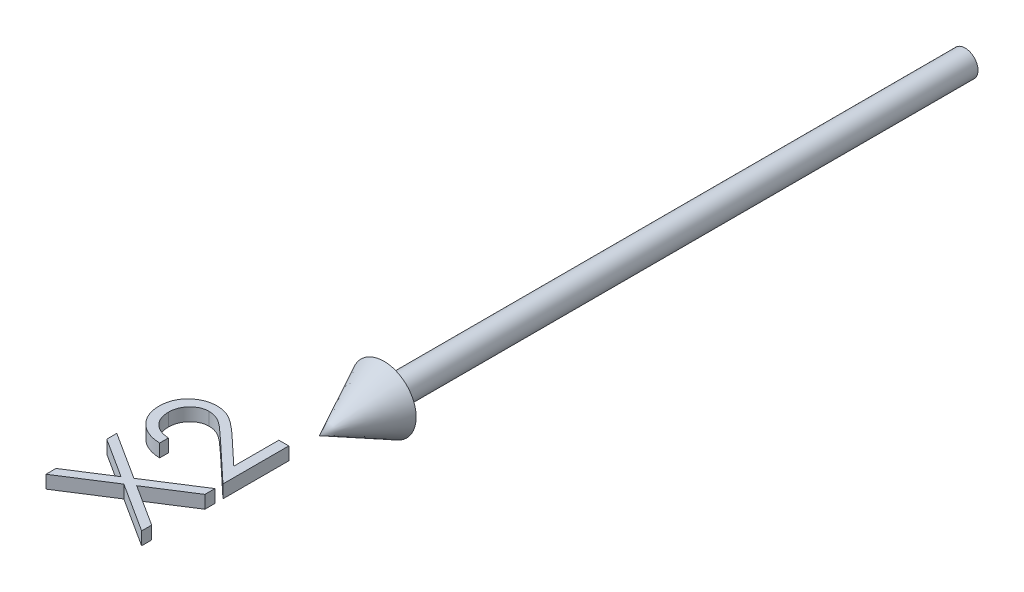
SolidWorks part; units mm, degrees
ref_plane "Front Plane" through (0, 0, 0) normal (0, 0, 1) x (1, 0, 0)
ref_plane "Top Plane" through (0, 0, 0) normal (0, 1, 0) x (1, 0, 0)
ref_plane "Right Plane" through (0, 0, 0) normal (1, 0, 0) x (0, 0, -1)
sketch "Sketch2" plane through (0, 0, 0) normal (0, 1, 0) x (1, 0, 0)
  line L0 (0, 41.95) -> (0, -114.4521) construction
  line L1 (-36.8894, 0) -> (41.4965, 0) construction
  line L2 (0, -100) -> (5, -90)
  line L3 (5, -90) -> (2, -90)
  line L4 (2, -90) -> (2, 0)
  line L5 (2, 0) -> (0, 0)
  line L6 (0, 0) -> (0, -100)
  dimension "D1" = 100
  dimension "D2" = 2
  dimension "D3" = 10
  dimension "D4" = 5
revolve "Revolve1" add sketch "Sketch2" angle 360 about L0
sketch "Sketch3" plane through (0, 0, 0) normal (0, 1, 0) x (1, 0, 0)
  line L0 (0, -103.9528) -> (0, -147.2622) construction
  line L1 (-18.6107, -118.3811) -> (18.3141, -118.3811) construction
  text T0 "X2" font "Century Gothic" height 15
extrude "Boss-Extrude1" add sketch "Sketch3" against normal blind 1 and the other way blind 1 separate body
equation "\"frame_arrow_length\"=100"
equation "\"D1@Sketch2\"=\"frame_arrow_length\""
equation "\"frame_arrow_odA\"=4"
equation "\"D2@Sketch2\"=\"frame_arrow_odA\"/2"
equation "\"frame_arrow_head_od\"=5"
equation "\"D4@Sketch2\"=\"frame_arrow_head_od\""
equation "\"frame_arrow_head_length\"=10"
equation "\"D3@Sketch2\"=\"frame_arrow_head_length\""
equation "\"tvarobot_theta1\"=30"
equation "\"link0_ringA_odA\"= 40"
equation "\"link0_ringA_odB\"= 25"
equation "\"link0_ringA_id\"= 20"
equation "\"link0_ringA_thickness\"= (\"link0_ringA_odB\" - \"link0_ringA_id\")/2"
equation "\"link0_ringA_height\"= 3"
equation "\"link0_ringA_heightA\"= 1.5"
equation "\"link0_ringA_heightB\"=\"link0_ringA_height\"-\"link0_ringA_heightA\""
equation "\"link0_ringB_odA\"= 40"
equation "\"link0_ringB_odB\"= 29"
equation "\"link0_ringB_id\"= \"link0_shaftA_bearing_id\"+1"
equation "\"link0_ringB_thickness\"= (\"link0_ringB_odB\" - \"link0_ringB_id\")/2"
equation "\"link0_ringB_height\"= 3"
equation "\"link0_ringB_heightA\"= 1.5"
equation "\"link0_ringB_heightB\"=\"link0_ringB_height\"-\"link0_ringB_heightA\""
equation "\"link0_shaftA_bearing_od\"=27"
equation "\"link0_shaftA_bearing_id\"=20"
equation "\"link0_shaftA_thrust_bearing_od\"=35"
equation "\"link0_shaftA_thrust_bearing_id\"=20.04"
equation "\"link0_shaftA_retaining_ring_id\"=18.5"
equation "\"link0_shaftA_retaining_ring_groove_width\"=1.5"
equation "\"link0_shaftA_spline_length\"=8.0"
equation "\"link0_shaftA_spline_depth\"=1.0"
equation "\"link0_shaftA_spline_width\"=4.0"
equation "\"link0_shaftA_odA\"=\"link0_shaftA_bearing_id\""
equation "\"link0_shaftA_odB\"=35"
equation "\"link0_shaftA_odC\"=\"link0_shaftA_bearing_id\""
equation "\"link0_shaftA_odD\"=\"link0_shaftA_odC\"-2*\"link0_shaftA_spline_depth\""
equation "\"link0_shaftA_odE\"=\"link0_shaftA_bearing_id\""
equation "\"link0_shaftA_odF\"=\"link0_shaftA_odE\"-2*\"link0_shaftA_spline_depth\""
equation "\"link0_shaftA_idA\"=10"
equation "\"link0_shaftA_idB\"=6"
equation "\"link0_shaftA_length\"=39.5"
equation "\"link0_shaftA_lengthA\"=8.0"
equation "\"link0_shaftA_lengthB\"=12.0"
equation "\"link0_shaftA_lengthC\"=35.0"
equation "\"link0_shaftA_lengthD\"=39.0"
equation "\"link0_shaftA_lengthE\"=\"link0_shaftA_length\"-\"link0_shaftA_lengthD\""
equation "\"link0_shaftA_offsetX\"=11"
equation "\"link0_shaftA_offsetY\"=0"
equation "\"link0_shaftA_bolt_pattern_dia\"=14"
equation "\"link0_motor_center_dist\"=26"
equation "\"link0_46t_pulley_spline_length\"=8"
equation "\"link0_46t_pulley_spline_depth\"=\"link0_shaftA_spline_depth\"*1.025"
equation "\"link0_46t_pulley_spline_width\"=\"link0_shaftA_spline_width\"*1.05"
equation "\"link0_46t_pulley_idA\"=\"link0_shaftA_bearing_id\"*1.025"
equation "\"link0_46t_pulley_idB\"=\"link0_46t_pulley_idA\"-2*\"link0_46t_pulley_spline_depth\""
equation "\"link0_shaftB_spline_length\"=10"
equation "\"link0_shaftB_spline_depth\"=1.0"
equation "\"link0_shaftB_spline_width\"=1.25"
equation "\"link0_shaftB_length\"=7"
equation "\"link0_shaftB_lengthA\"=1.5"
equation "\"link0_shaftB_lengthB\"=2.75"
equation "\"link0_shaftB_odA\"=32"
equation "\"link0_shaftB_odB\"=22"
equation "\"link0_shaftB_odC\"=20"
equation "\"link0_shaftB_idA\"=10"
equation "\"link0_shaftB_bolt_diameter\"=19"
equation "\"link0_shaftB_bearing_od\"=27"
equation "\"link0_shaftB_bearing_id\"=20"
equation "\"link0_motor_length\"=46.5"
equation "\"link0_motor_width\"=28.5"
equation "\"link0_motor_height\"=34"
equation "\"link0_motor_offset\"=8"
equation "\"link0_shellA_thickness\"=2.5"
equation "\"link0_shellB_thickness\"=\"link0_shellA_thickness\""
equation "\"link0_plateA_shellA_height\"=48"
equation "\"link0_shellA_width\" =\"link0_plateA_width\""
equation "\"link0_shellA_height\" = \"link0_plateA_shellA_height\"-\"link0_plateA_height\""
equation "\"link0_shellA_length\" = \"link0_plateA_lengthB\" "
equation "\"link0_shellB_length\"=\"link0_shellA_length\""
equation "\"link0_shellA_radius\" = 0.375*25.4"
equation "\"link0_shellA_radiusA\"= \"link0_plateA_radiusA\""
equation "\"link0_shellA_radiusB\"= \"link0_plateA_radiusB\""
equation "\"link0_shellA_radiusC\"= 3"
equation "\"link0_postA_height\"=7"
equation "\"link0_postA_width\"=16"
equation "\"link0_postA_length\"=20"
equation "\"link0_postA_posX\"=22"
equation "\"link0_postA_posY\"=17.5"
equation "\"link0_postA_pocket_width\"=6.0"
equation "\"link0_postA_pocket_length\"=2.5"
equation "\"link0_postA_pocket_depth\"=9"
equation "\"link0_postA_pocket_posZ\"=10"
equation "\"link0_postB_height\"=7"
equation "\"link0_postB_width\"=16"
equation "\"link0_postB_length\"=20"
equation "\"link0_postB_posX\"=22"
equation "\"link0_postB_posY\"=17.5"
equation "\"link0_postB_id\"=3.0"
equation "\"link0_postB_pocket_width\"=6.0"
equation "\"link0_postB_pocket_length\"=2.5"
equation "\"link0_postB_pocket_depth\"=9"
equation "\"link0_postB_pocket_posZ\"=10"
equation "\"link0_postC_height\"=7"
equation "\"link0_postC_width\"=16"
equation "\"link0_postC_length\"=20"
equation "\"link0_postC_posX\"=22"
equation "\"link0_postC_posY\"=17.5"
equation "\"link0_postC_id\"=3.0"
equation "\"link0_postC_pocket_width\"=6.0"
equation "\"link0_postC_pocket_length\"=2.5"
equation "\"link0_postC_pocket_depth\"=9"
equation "\"link0_postC_pocket_posZ\"=10"
equation "\"link0_postD_height\"=7"
equation "\"link0_postD_width\"=16"
equation "\"link0_postD_length\"=20"
equation "\"link0_postD_posX\"=22"
equation "\"link0_postD_posY\"=17.5"
equation "\"link0_postD_id\"=3.0"
equation "\"link0_postD_pocket_width\"=6.0"
equation "\"link0_postD_pocket_length\"=3.0"
equation "\"link0_postD_pocket_depth\"=9"
equation "\"link0_postD_pocket_posZ\"=10"
equation "\"link0_postE_height\"=5"
equation "\"link0_postE_width\"=16"
equation "\"link0_postE_length\"=\"link0_plateE_lengthA\"-\"link0_lip_height\""
equation "\"link0_postE_posZ\"=22"
equation "\"link0_postE_posX\"=17.5"
equation "\"link0_postE_posY\"=22"
equation "\"link0_postE_id\"=3.0"
equation "\"link0_postE_cbore_id\"=6.5"
equation "\"link0_postE_hole_id\"=3"
equation "\"link0_postF_posZ\"=22"
equation "\"link0_postF_posX\"=17.5"
equation "\"link0_postF_posY\"=\"link0_plateB_lengthA\"+4"
equation "\"link0_postF_id\"=3.0"
equation "\"link0_postF_cbore_id\"=6.5"
equation "\"link0_postF_hole_id\"=3"
equation "\"link0_postG_posZ\"=22"
equation "\"link0_postG_posX\"=17.5"
equation "\"link0_postG_posY\"=\"link0_plateB_lengthA\"+12"
equation "\"link0_postG_id\"=3.0"
equation "\"link0_postG_cbore_id\"=6.5"
equation "\"link0_postG_hole_id\"=3"
equation "\"link0_postHIJ_posY\"=6"
equation "\"link0_postH_posX\"=28"
equation "\"link0_postH_posY\"=20"
equation "\"link0_postH_posZ\"=20"
equation "\"link0_postH_length\"=10"
equation "\"link0_postI_posX\"=28"
equation "\"link0_postI_posY\"=20"
equation "\"link0_postI_posZ\"=135"
equation "\"link0_postI_length\"=10"
equation "\"link0_postJ_posX\"=28"
equation "\"link0_postJ_posY\"=20"
equation "\"link0_postJ_posZ\"=175"
equation "\"link0_postJ_length\"=10"
equation "\"link0_postK_posX\"=28"
equation "\"link0_postK_posY\"=20"
equation "\"link0_postK_posZ\"=175"
equation "\"link0_postK_length\"=10"
equation "\"link0_postL_posX\"=28"
equation "\"link0_postL_posY\"=20"
equation "\"link0_postL_posZ\"=135"
equation "\"link0_postL_length\"=10"
equation "\"link0_postM_posX\"=28"
equation "\"link0_postM_posY\"=20"
equation "\"link0_postM_posZ\"=35"
equation "\"link0_postM_length\"=10"
equation "\"link0_plateA_lengthA\"=30"
equation "\"link0_plateA_lengthB\"=150"
equation "\"link0_plateA_lengthC\"=30"
equation "\"link0_plateA_length\"=\"link0_plateA_lengthA\"+\"link0_plateA_lengthB\"+\"link0_plateA_lengthC\""
equation "\"link0_plateA_width\"=  68"
equation "\"link0_plateA_height\"= \"link0_plateA_radiusA\""
equation "\"link0_plateA_thickness\"=\"link0_shellA_thickness\""
equation "\"link0_plateA_radius\"= 9.5"
equation "\"link0_plateA_radiusA\"= 18"
equation "\"link0_plateA_radiusB\"= 18"
equation "\"link0_plateA_radiusC\"= 3"
equation "\"link0_plateB_length\"= 40"
equation "\"link0_plateB_width\"= \"link0_plateA_width\"*1.005"
equation "\"link0_plateB_height\"= \"link0_plateA_shellA_height\"*1.005"
equation "\"link0_plateB_lengthA\"=\"link0_lip_height\"+\"link0_plateD_thickness\"+\"link0_motor_mount_thickness\""
equation "\"link0_plateB_lengthB\"=\"link0_plateB_height\"-\"link0_plateB_lengthA\""
equation "\"link0_plateB_radiusA\"= \"link0_plateA_radiusA\""
equation "\"link0_plateB_radiusB\"= \"link0_plateA_radiusB\""
equation "\"link0_plateB_radiusC\"= 3"
equation "\"link0_plateB_idA\"=\"link0_shaftA_odC\"+1"
equation "\"link0_plateB_idB\"=\"link0_shaftA_bearing_od\"-2"
equation "\"link0_plateB_idC\"=\"link0_shaftA_bearing_od\"*1.005"
equation "\"link0_plateB_idD\"=\"link0_shaftA_thrust_bearing_od\"+1 "
equation "\"link0_plateB_depthA\"=1.0"
equation "\"link0_plateB_depthB\"=2.0"
equation "\"link0_plateB_depthC\"=8"
equation "\"link0_plateB_depthD\"=\"link0_plateB_length\"-\"link0_lip_height\"-\"link0_plateD_thickness\" "
equation "\"link0_plateC_length\"=\"link0_plateB_length\""
equation "\"link0_plateC_width\"= \"link0_plateB_width\""
equation "\"link0_plateC_height\"= .1*25.4"
equation "\"link0_plateA_hole_od\" = 0.1*25.4"
equation "\"link0_plateA_hole_delx\" = 0.5*25.4"
equation "\"link0_plateA_hole_delz\" = 0.75*25.4"
equation "\"link0_plateA_hole_offx\" = 0.0*25.4"
equation "\"link0_plateA_hole_offz\" = \"link0_plateA_length\"/2"
equation "\"link0_plateB_hole_od\" = 0.1*25.4"
equation "\"link0_plateB_hole_delx\"= 0.75*25.4"
equation "\"link0_plateB_hole_delz\"= 0.75*25.4"
equation "\"link0_plateB_hole_offx\"= 0.0*25.4"
equation "\"link0_plateB_hole_offz\"= 0.0*25.4"
equation "\"link0_plateC_hole_od\"= 0.1*25.4"
equation "\"link0_plateC_hole_delx\"= 0.75*25.4"
equation "\"link0_plateC_hole_delz\"= 0.75*25.4"
equation "\"link0_plateC_hole_offx\"= 0.0*25.4"
equation "\"link0_plateC_hole_offz\"= 0.0*25.4"
equation "\"link0_plateD_height\"=\"link0_plateB_height\"-2*\"link0_shellA_thickness\""
equation "\"link0_plateD_width\"=\"link0_plateB_width\"-2*\"link0_shellA_thickness\""
equation "\"link0_plateD_thickness\"=10"
equation "\"link0_plateD_radiusA\"=\"link0_plateB_radiusA\"-\"link0_shellA_thickness\""
equation "\"link0_plateD_odA\"= .375*25.4"
equation "\"link0_plateD_odB\"= .375*25.4"
equation "\"link0_plateD_bearing_id\"=20"
equation "\"link0_plateD_bearing_od\"=27"
equation "\"link0_plateE_radiusA\"=\"link0_plateA_radiusA\""
equation "\"link0_plateE_radiusB\"=\"link0_plateA_radiusB\""
equation "\"link0_plateE_radiusC\"=8.0"
equation "\"link0_plateE_length\"=30"
equation "\"link0_plateE_lengthA\"=16"
equation "\"link0_plateE_height\"=\"link0_plateB_height\""
equation "\"link0_plateE_width\"=\"link0_plateB_width\""
equation "\"link0_plateE_odA\"=\"gantry_coupler_id\"*0.99"
equation "\"link0_plateE_idA\"=\"link0_plateE_odA\"-20.0"
equation "\"link0_plateE_spline_depth\"=\"link0_poleA_spline_depth\"*1.05"
equation "\"link0_plateE_spline_width\"=\"link0_poleA_spline_width\"*1.075"
equation "\"link0_plateE_spline_length\"=\"link0_poleA_spline_length\""
equation "\"link0_plateE_coupler_length\"=46"
equation "\"link0_lip_height\"=5.0"
equation "\"link0_lip_thickness\"=2.0"
equation "\"link0_motor_mount_thickness\"=8.0"
equation "\"link0_motor_mount_idA\"=22"
equation "\"link0_motor_mount_idB\"=\"link0_shaftB_bearing_od\"*1.005"
equation "\"link0_motor_mount_idC\"=\"link0_shaftB_bearing_od\"-2"
equation "\"link0_motor_mount_depthA\"=5.5"
equation "\"link0_motor_mount_height\"=\"link0_plateD_height\""
equation "\"link0_motor_mount_width\"=\"link0_plateD_width\""
equation "\"link0_motor_mountL_height\"=36"
equation "\"link0_motor_mountL_heightA\"=12"
equation "\"link0_motor_mountL_length\"=50"
equation "\"link0_motor_mountL_lengthA\"=36"
equation "\"gantry_coupler_od\"=25.4*2.0"
equation "\"gantry_coupler_id\"=1.645*25.4"
equation "\"gantry_coupler_offsetX\"=\"link0_plateE_width\"/2"
equation "\"link0_poleA_odA\"=20"
equation "\"link0_poleA_odB\"=36"
equation "\"link0_poleA_idA\"=\"link0_poleA_odA\"-2*\"link0_poleA_thickness\""
equation "\"link0_poleA_idB\"=(\"link0_plateE_idA\"/2+1.5*\"link0_lip_thickness\")*1.04"
equation "\"link0_poleA_thickness\"=3.5"
equation "\"link0_poleA_length\"=100"
equation "\"link0_poleA_lengthA\"=18.5"
equation "\"link0_poleA_lengthB\"=80"
equation "\"link0_poleA_gasket_thickness\"=1.5"
equation "\"link0_poleA_spline_depth\"=1.0"
equation "\"link0_poleA_spline_width\"=4.0"
equation "\"link0_poleA_spline_length\"=10.0"
equation "\"link1_plateB_length\"=30"
equation "\"link1_lip_height\"=\"link0_lip_height\""
equation "\"link0_tension_plateA_width\"=12"
equation "\"link0_tension_plateA_lengthA\"=10.5"
equation "\"link0_tension_plateB_width\"=\"link0_tension_plateA_width\""
equation "\"link0_tension_plateB_lengthA\"=\"link0_tension_plateA_lengthA\""
equation "\"link0_tension_wheelA_posZ\"=7"
equation "\"link0_tension_wheelA_posX\"=\"link0_plateD_height\"/2-\"link0_tension_plateA_lengthA\""
equation "\"link0_m2_clear_hole_id\"=2.35"
equation "\"link0_m2_insert_hole_id\"=2.5"
equation "\"link0_m2_tap_hole_id\"=1.75"
equation "\"link0_m2_nut_socket_width\"=4.25"
equation "\"link0_m2_nut_socket_depth\"=2.5"
equation "\"link0_m2_cbore_id\"=3.75"
equation "\"link0_m2_cbore_depth\"=7"
equation "\"link0_m2_5_clear_hole_id\"=2.75"
equation "\"link0_m2_5_insert_hole_id\"=2.75"
equation "\"link0_m2_5_tap_hole_id\"=2.25"
equation "\"link0_m2_5_nut_socket_width\"=5.25"
equation "\"link0_m2_5_nut_socket_depth\"=2.5"
equation "\"link0_m2_5_cbore_id\"=4.75"
equation "\"link0_m2_5_cbore_depth\"=2.5"
equation "\"link0_m2_5_insert_access_length\"=6.0"
equation "\"link0_m2_5_insert_access_width\"=3.0"
equation "\"link0_m3_clear_hole_id\"=3.25"
equation "\"link0_m3_insert_hole_id\"=3"
equation "\"link0_m3_tap_hole_id\"=2.75"
equation "\"link0_m3_nut_socket_width\"=5.75"
equation "\"link0_m3_nut_socket_depth\"=4.0"
equation "\"link0_m3_cbore_id\"=5.75"
equation "\"link0_m3_cbore_depth\"=3.5"
equation "\"link0_m3_insert_access_length\"=4.5"
equation "\"link0_m3_insert_access_width\"=3.5"
equation "\"link0_rpi_mount_height\"=6"
equation "\"link0_rpi_mount_width\"=49"
equation "\"link0_rpi_mount_length\"=58"
equation "\"link0_rpi_mount_post_od\"=6"
equation "\"link0_rpi_mount_posZ\"=72"
equation "\"link0_rpi_mount_posX\"=11.5"
equation "\"link0_mcu_mount_height\"=5"
equation "\"link0_mcu_mount_width\"=49"
equation "\"link0_mcu_mount_length\"=58"
equation "\"link0_mcu_mount_post_od\"=6"
equation "\"link0_mcu_mount_posZ\"=164"
equation "\"link0_mcu_mount_posX\"=4"
equation "\"link0_pwr_mount_height\"=4"
equation "\"link0_pwr_mount_width\"=15.75"
equation "\"link0_pwr_mount_length\"=75.75"
equation "\"link0_pwr_mount_post_od\"=6"
equation "\"link0_pwr_mount_posZ\"=75"
equation "\"link0_pwr_mount_posX\"=16"
equation "\"link0_pwr_board_height\"=6"
equation "\"link0_pwr_board_width\"=21"
equation "\"link0_pwr_board_length\"=80"
